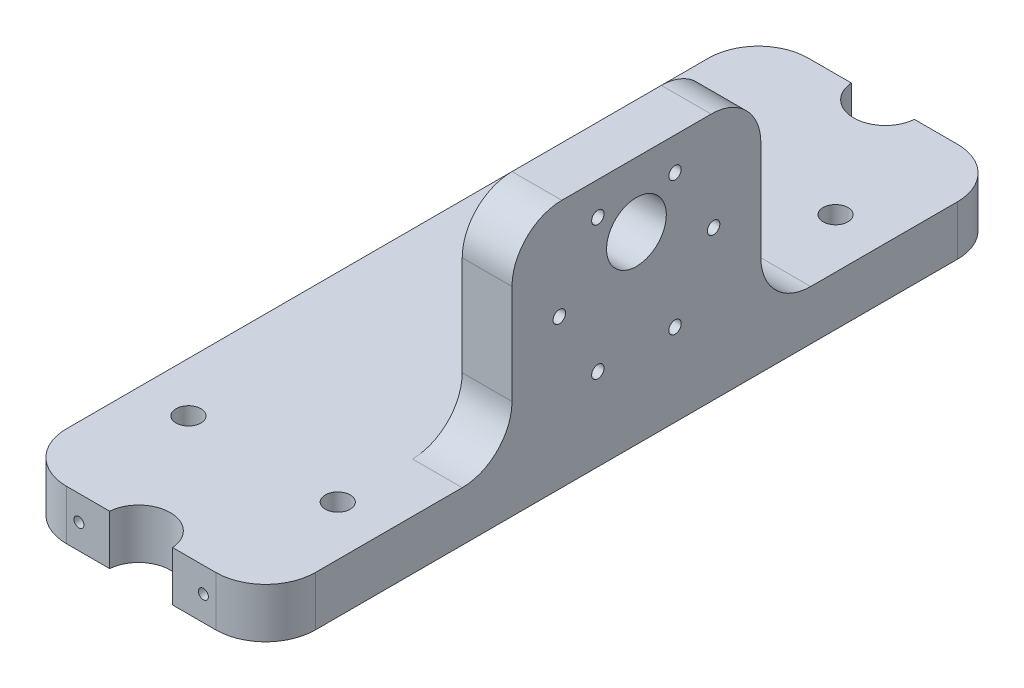
SolidWorks part; units mm, degrees
material "Nylon 101"
ref_plane "Front" through (0, 0, 0) normal (0, 0, 1) x (1, 0, 0)
ref_plane "Top" through (0, 0, 0) normal (0, 1, 0) x (1, 0, 0)
ref_plane "Right" through (0, 0, 0) normal (1, 0, 0) x (0, 0, -1)
sketch "Sketch1" plane through (0, 0, 0) normal (0, 1, 0) x (1, 0, 0)
  line L0 (-25, -75) -> (25, -75) construction
  line L1 (-15, 50) -> (15, 50) construction
  line L2 (0, -75) -> (0, 75) construction
  line L3 (-25, -75) -> (-25, 75)
  line L4 (25, -75) -> (25, 75)
  line L5 (25, 0) -> (0, 0) construction
  line L6 (25, 17) -> (97.2, 17)
  line L7 (25, 17) -> (25, -17)
  line L8 (25, -17) -> (97.2, -17)
  line L9 (97.2, 17) -> (97.2, -17)
  line L10 (-15, 50) -> (-15, -50) construction
  line L11 (-15, -50) -> (15, -50) construction
  line L12 (15, 50) -> (15, -50) construction
  line L13 (-25, -75.5) -> (25, -75.5)
  line L14 (-25, -74.5) -> (25, -74.5)
  line L15 (-25, 75.5) -> (25, 75.5)
  line L16 (-25, 74.5) -> (25, 74.5)
  circle A0 centre (0, 75) radius 6.35
  circle A1 centre (0, -75) radius 6.35
  arc A2 (-25, -75) -> (25, -75) centre (0, -75) ccw
  arc A3 (25, 75) -> (-25, 75) centre (0, 75) ccw
  circle A6 centre (-15, 50) radius 2.5
  circle A7 centre (-15, -50) radius 2.5
  circle A8 centre (15, -50) radius 2.5
  circle A9 centre (15, 50) radius 2.5
  point P8 (0, 0)
  point P24 (0, -50)
  dimension "D2" = 12.7
  dimension "D5" = 25
  dimension "D1" = 5
  dimension "D3" = 150
  dimension "D4" = 25
  dimension "D6" = 25
  dimension "D7" = 34
  dimension "D8" = 72.2
  dimension "D9" = 30
  dimension "D10" = 0.5
  dimension "D11" = 0.5
extrude "Boss-Extrude1" add sketch "Sketch1" along normal blind 10 contours A1 L14 L4 L16 A0 L3 A9 A8 A7 A6 region at (0, 0, 0)
sketch "Sketch2" plane through (0, 0, 0) normal (0, 1, 0) x (1, 0, 0)
  line L0 (25, -75) -> (25, 75) construction
  line L1 (25, 25) -> (15, 25)
  line L2 (25, 25) -> (25, -25)
  line L3 (25, -25) -> (15, -25)
  line L4 (15, 25) -> (15, -25)
  line L6 (25, 0) -> (0, 0) construction
  line L7 (25, 0) -> (0, 0) construction
  dimension "D1" = 50
  dimension "D2" = 10
extrude "Boss-Extrude2" add sketch "Sketch2" along normal blind 50
sketch "Sketch3" plane through (25, 0, 0) normal (1, 0, 0) x (0, 0, -1)
  line L0 (-25, 10) -> (25, 10) construction
  line L1 (0, 10) -> (0, 50) construction
  line L3 (-25, 50) -> (25, 50) construction
  circle A0 centre (0, 30) radius 15.5 construction
  circle A1 centre (0, 30) radius 18.4 construction
  circle A2 centre (-15.5, 30) radius 1.25
  circle A8 centre (0, 37) radius 3 construction
  circle A9 centre (0, 37) radius 6
  circle A10 centre (-7.75, 43.4234) radius 1.25
  circle A11 centre (7.75, 43.4234) radius 1.25
  circle A12 centre (15.5, 30) radius 1.25
  circle A13 centre (7.75, 16.5766) radius 1.25
  circle A14 centre (-7.75, 16.5766) radius 1.25
  dimension "D1" = 31
  dimension "D2" = 2.5
  dimension "D3" = 36.8
  dimension "D4" = 12
  dimension "D6" = 6
  dimension "D7" = 6
  dimension "D5" = 7
extrude "Cut-Extrude1" cut sketch "Sketch3" against normal blind 25
fillet "Fillet1" radius 10 8 edges at (-25, 5, -74.5) (25, 5, -74.5) (-25, 5, 74.5) (25, 5, 74.5) (20, 10, -25) (20, 50, -25) (20, 50, 25) (20, 10, 25)
sketch "Sketch4" plane through (0, 0, 74.5) normal (0, 0, 1) x (1, 0, 0)
  line L0 (-12.5, 0) -> (-12.5, 10) construction
  line L1 (-15, 0) -> (-6.3303, 0) construction
  line L2 (12.5, 10) -> (12.5, 0) construction
  line L3 (6.3303, 0) -> (15, 0) construction
  line L8 (-15, 10) -> (-6.3303, 10) construction
  line L9 (6.3303, 10) -> (15, 10) construction
  circle A0 centre (-12.5, 5) radius 1
  circle A1 centre (12.5, 5) radius 1
  dimension "D1" = 2
  dimension "D2" = 12.5
  dimension "D3" = 12.5
extrude "Cut-Extrude2" cut sketch "Sketch4" against normal blind 5
extrude "Cut-Extrude3" cut sketch "Sketch4<2>" along normal blind 5 from surface starting at face at (10.6651, 5, -74.5)
sketch "Sketch4<2>" plane through (0, 0, 74.5) normal (0, 0, 1) x (1, 0, 0) same geometry as "Sketch4"
